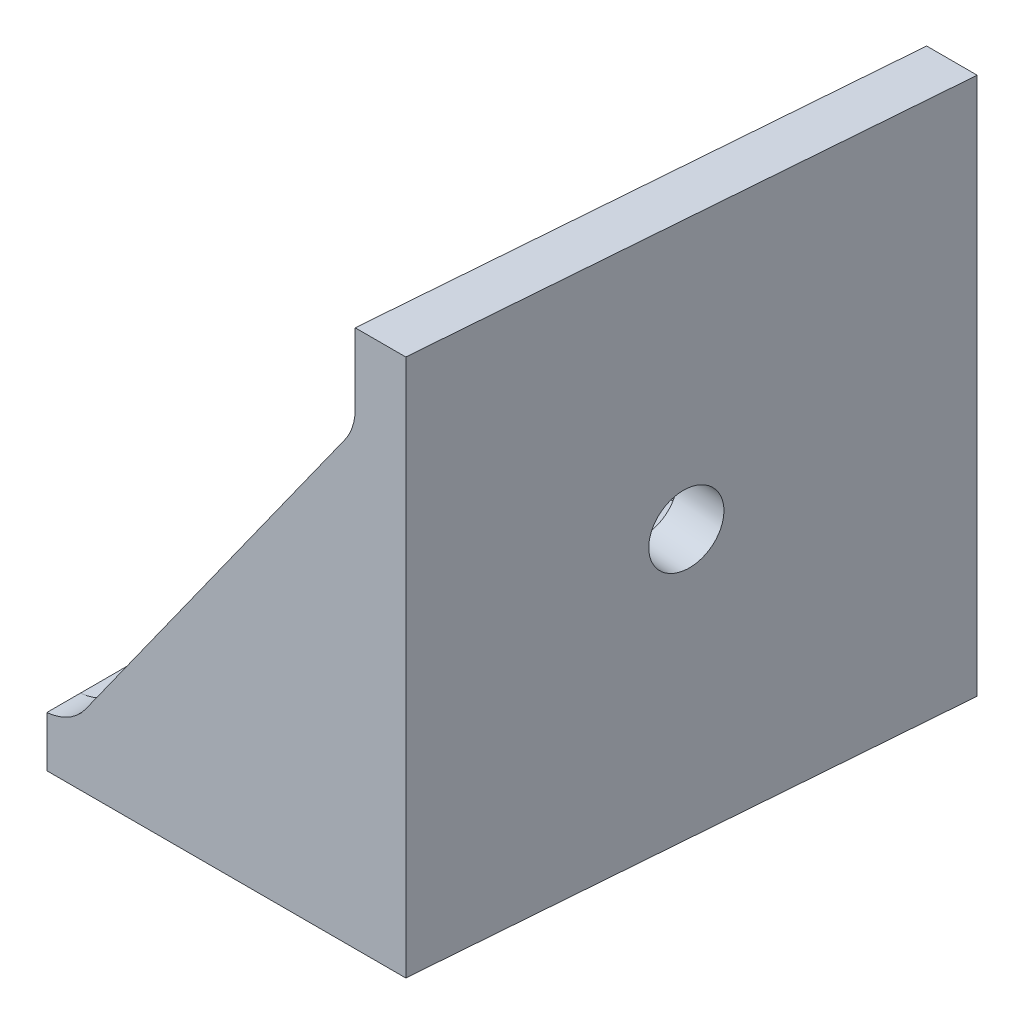
SolidWorks part; units mm, degrees
ref_plane "Front Plane" through (0, 0, 0) normal (0, 0, 1) x (1, 0, 0)
ref_plane "Top Plane" through (0, 0, 0) normal (0, 1, 0) x (1, 0, 0)
ref_plane "Right Plane" through (0, 0, 0) normal (1, 0, 0) x (0, 0, -1)
sketch "Sketch1" plane through (0, 0, 0) normal (0, 1, 0) x (1, 0, 0)
  line L0 (37.846, 50.038) -> (33.9079, 0)
  line L1 (0, 0) -> (33.9079, 0)
  line L2 (0, 0) -> (0, 50.038)
  line L3 (0, 50.038) -> (37.846, 50.038)
  circle A0 centre (12.7, 37.338) radius 2.667
  circle A1 centre (25.4, 37.338) radius 2.667
  circle A2 centre (12.7, 11.938) radius 2.667
  circle A3 centre (25.4, 11.938) radius 2.667
  point P15 (41.5094, 22.4737)
  dimension "D3" = 5.334
  dimension "D4" = 5.334
  dimension "D5" = 5.334
  dimension "D6" = 5.334
  dimension "D10" = 12.7
  dimension "D11" = 12.7
  dimension "D14" = 25.4
  dimension "D15" = 25.4
  dimension "D1" = 85.5
  dimension "D2" = 50.038
  dimension "D7" = 12.7
  dimension "D8" = 12.7
  dimension "D9" = 37.846
  dimension "D12" = 12.7
  dimension "D13" = 12.7
extrude "Boss-Extrude1" add sketch "Sketch1" along normal blind 4.7625
sketch "Sketch2" plane through (0, 0, 0) normal (0, -1, 0) x (1, 0, 0)
  line L1 (33.0688, -50.038) -> (37.846, -50.038)
  line L2 (29.1601, -0.3737) -> (33.0982, -50.4117)
  line L3 (29.1601, -0.3737) -> (33.0688, -50.038)
  line L4 (37.846, -50.038) -> (0, -50.038) construction
  line L5 (37.846, -50.038) -> (33.9079, 0)
  line L7 (29.2288, -1.2469) -> (29.1307, 0)
  line L8 (0, 0) -> (33.9079, 0) construction
  line L9 (29.1307, 0) -> (33.9079, 0)
  line M5 (0, -50.038) -> (37.846, -50.038)
  line M6 (37.846, -50.038) -> (33.9079, 0)
  line M7 (33.9079, 0) -> (0, 0)
  dimension "D1" = 4.7625
extrude "Boss-Extrude2" add sketch "Sketch2" against normal blind 50.8 contours L7 L3 M5 M6 M7 region at (33.4883, 0, -25.019)
sketch "Sketch4" plane through (28.9514, 0, 2.2785) normal (-0.9969, 0, -0.0785) x (-0.0785, 0, 0.9969)
  line L0 (-2.2856, 50.8) -> (-2.2856, 4.7625) construction
  line L1 (-52.4783, 50.8) -> (-2.2856, 50.8) construction
  circle A0 centre (-27.3046, 25.4) radius 3.302
  dimension "D1" = 6.604
  dimension "D2" = 25.019
  dimension "D3" = 25.4
extrude "Cut-Extrude1" cut sketch "Sketch4" against normal blind 55.626
sketch "Sketch5" plane through (0, 0, 0) normal (0, 0, 1) x (1, 0, 0)
  line L0 (2.1579, 4.7625) -> (33.9079, 16.3186)
  line L1 (0, 4.7625) -> (29.1307, 4.7625) construction
  line L2 (33.9079, 50.8) -> (33.9079, 0) construction
  line L3 (33.9079, 16.3186) -> (33.9079, 4.7625)
  line L4 (33.9079, 4.7625) -> (2.1579, 4.7625)
  dimension "D1" = 31.75
  dimension "D2" = 20
extrude "Boss-Extrude3" add sketch "Sketch5" against normal blind 50.038
sketch "Sketch7" plane through (0, 50.8, 0) normal (0, 1, 0) x (1, 0, 0)
  line L0 (33.0688, 50.038) -> (31.2247, 26.6065)
  line L1 (33.0688, 50.038) -> (29.1307, 0) construction
  line L2 (31.2247, 26.6065) -> (2.1579, 26.6065)
  line L3 (2.1579, 50.038) -> (2.1579, 0) construction
  line L4 (2.1579, 26.6065) -> (2.1579, 50.038)
  line L5 (2.1579, 50.038) -> (33.0688, 50.038)
  line L6 (2.1579, 23.4315) -> (30.9748, 23.4315)
  line L7 (30.9748, 23.4315) -> (29.1307, 0)
  line L8 (29.1307, 0) -> (2.1579, 0)
  line L9 (2.1579, 0) -> (2.1579, 23.4315)
  dimension "D1" = 23.4315
  dimension "D2" = 23.4315
extrude "Cut-Extrude5" cut sketch "Sketch7" against normal up to surface (46.0375 mm away) up to face at (1.079, 4.7625, -25.019)
sketch "Sketch8" plane through (0, 0, 0) normal (0, 0, 1) x (1, 0, 0)
  line L0 (2.1579, 4.7625) -> (33.9079, 49.2125)
  line L1 (33.9079, 50.8) -> (33.9079, 0) construction
  line L2 (33.9079, 49.2125) -> (33.9079, 4.7625)
  line L3 (33.9079, 4.7625) -> (2.1579, 4.7625)
  dimension "D1" = 44.45
extrude "Boss-Extrude4" add sketch "Sketch8" against normal blind 3.175
sketch "Sketch9" plane through (0, 0, -50.038) normal (0, 0, -1) x (-1, 0, 0)
  line L0 (-2.1579, 4.7625) -> (-33.0688, 47.9425)
  line L1 (-33.0688, 50.8) -> (-33.0688, 4.7625) construction
  line L2 (-33.0688, 47.9425) -> (-33.0688, 4.7625)
  line L3 (-33.0688, 4.7625) -> (-2.1579, 4.7625)
  dimension "D1" = 43.18
extrude "Boss-Extrude5" add sketch "Sketch9" against normal blind 3.175
fillet "Fillet1" radius 5.08 4 edges at (2.1579, 4.7625, -1.5875) (2.1579, 4.7625, -48.4505) (29.2556, 42.6993, -1.5875) (32.9438, 47.768, -48.4505)
fillet "Fillet2" radius 5.08 2 edges at (32.8189, 27.0043, -46.863) (29.3806, 24.6433, -3.175)
